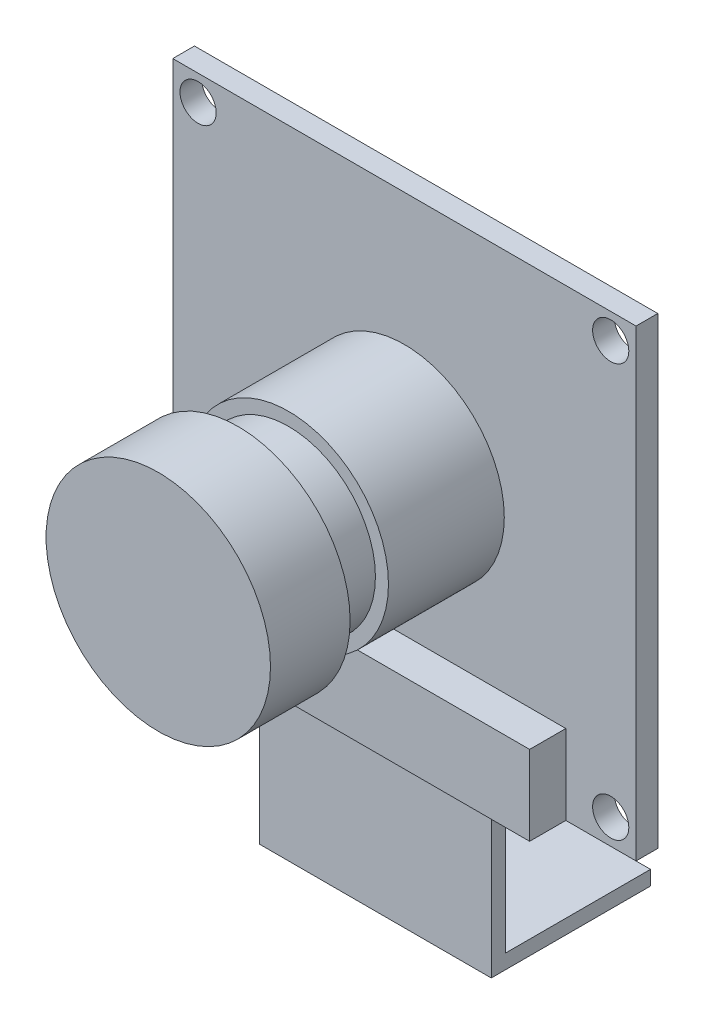
SolidWorks part; units mm, degrees
ref_plane "Спереди" through (0, 0, 0) normal (0, 0, 1) x (1, 0, 0)
ref_plane "Сверху" through (0, 0, 0) normal (0, 1, 0) x (1, 0, 0)
ref_plane "Справа" through (0, 0, 0) normal (1, 0, 0) x (0, 0, -1)
sketch "Эскиз1" plane through (0, 0, 0) normal (0, 0, 1) x (1, 0, 0)
  line L0 (0, 16) -> (0, -16) construction
  line L1 (-16, 16) -> (16, 16)
  line L2 (-16, 16) -> (-16, -16)
  line L3 (-16, -16) -> (16, -16)
  line L4 (16, 16) -> (16, -16)
  line L5 (-16, 16) -> (16, -16) construction
  line L6 (-16, -16) -> (16, 16) construction
  line L7 (-14.25, 14.25) -> (14.25, 14.25) construction
  line L8 (-14.25, 14.25) -> (-14.25, -14.25) construction
  line L9 (-14.25, -14.25) -> (14.25, -14.25) construction
  line L10 (14.25, 14.25) -> (14.25, -14.25) construction
  line L11 (-14.25, 14.25) -> (14.25, -14.25) construction
  line L12 (-14.25, -14.25) -> (14.25, 14.25) construction
  line L13 (-11.15, -10.5) -> (11.15, -10.5)
  line L14 (-11.15, -10.5) -> (-11.15, -16)
  line L15 (-11.15, -16) -> (11.15, -16)
  line L16 (11.15, -10.5) -> (11.15, -16)
  line L17 (-16, 0) -> (16, 0) construction
  circle A0 centre (0, 0) radius 6
  circle A1 centre (0, 0) radius 6.9
  circle A2 centre (0, 0) radius 7.75
  circle A4 centre (14.25, 14.25) radius 1.25
  circle A5 centre (14.25, -14.25) radius 1.25
  circle A6 centre (-14.25, -14.25) radius 1.25
  circle A7 centre (-14.25, 14.25) radius 1.25
  circle A9 centre (9.5, 0) radius 1.5
  circle A10 centre (-9.5, 0) radius 1.5
  point P0 (0, 0)
  point P6 (0, 0)
  point P23 (0, -16)
  point P34 (0, 0)
  dimension "D3" = 22.3
  dimension "D5" = 2.5
  dimension "D7" = 13.8
  dimension "D8" = 12
  dimension "D9" = 15.5
  dimension "D10" = 3
  dimension "D1" = 32
  dimension "D2" = 5.5
  dimension "D4" = 28.5
  dimension "D11" = 6.5
  dimension "D6" = 4
extrude "Плата камеры" add sketch "Эскиз1" along normal blind 1.5 contours L13 L16 L3 L4 L1 L2 L14 A7 A6 A5 A4 A2 | L16 L13 L14 L3 | A2 A1 | A1 A0 | A0 | A10 | A9 region at (0, 15.5475, 0) region at (0, -13.25, 0) region at (0, 0, 0) region at (-6.7048, 0, 0) region at (-7.5308, 0, 0) region at (-9.5, 0, 0)
extrude "Гнездо шлейфа" add sketch "Эскиз1<3>" along normal blind 2.5 from surface contours L16 L13 L14 L3 region at (0, -13.25, 0) starting at face at (0, 0, 1.5)
sketch "Эскиз1<3>" plane through (0, 0, 0) normal (0, 0, 1) x (1, 0, 0) same geometry as "Эскиз1"
extrude "Основа объектива" add sketch "Эскиз1<4>" along normal blind 8 from surface contours A1 A0 | A0 region at (0, 0, 0) region at (-6.7048, 0, 0) starting at face at (15.5, 14.25, 1.5)
sketch "Эскиз1<4>" plane through (0, 0, 0) normal (0, 0, 1) x (1, 0, 0) same geometry as "Эскиз1"
extrude "Резьбовая часть" add sketch "Эскиз1<5>" along normal blind 3.5 from surface contours A0 region at (0, 0, 0) starting at face at (6.9, 0, 9.5)
sketch "Эскиз1<5>" plane through (0, 0, 0) normal (0, 0, 1) x (1, 0, 0) same geometry as "Эскиз1"
extrude "Объектив(со стеклом)" add sketch "Эскиз1<6>" along normal blind 5.5 from surface contours A2 A1 | A1 A0 | A0 region at (0, 0, 0) region at (-6.7048, 0, 0) region at (-7.5308, 0, 0) starting at face at (6, 0, 13)
sketch "Эскиз1<6>" plane through (0, 0, 0) normal (0, 0, 1) x (1, 0, 0) same geometry as "Эскиз1"
extrude "Болты крепления объектива" add sketch "Эскиз1<7>" against normal blind 0.5 contours A9 | A10 region at (9.5, 0, 0) region at (-9.5, 0, 0)
sketch "Эскиз1<7>" plane through (0, 0, 0) normal (0, 0, 1) x (1, 0, 0) same geometry as "Эскиз1"
sketch "Эскиз2" plane through (0, -16, 0) normal (0, -1, 0) x (1, 0, 0)
  line L0 (-16, 0) -> (16, 0) construction
  line L1 (-8, 3.5) -> (8, 3.5)
  line L2 (-8, 3.5) -> (-8, 2.5)
  line L3 (-8, 2.5) -> (8, 2.5)
  line L4 (8, 3.5) -> (8, 2.5)
  line L5 (-8, 3.5) -> (8, 2.5) construction
  line L6 (-8, 2.5) -> (8, 3.5) construction
  point P0 (0, 3)
  dimension "D1" = 16
  dimension "D2" = 1
  dimension "D3" = 2.5
extrude "Шлейф" add sketch "Эскиз2" along normal blind 10 contours L4 L1 L2 L3 region at (0, -16, 3)
sketch "Эскиз3" plane through (0, 0, 2.5) normal (0, 0, -1) x (-1, 0, 0)
  line L0 (-8, -26) -> (-8, -16) construction
  line L1 (-8, -25) -> (8, -25)
  line L2 (-8, -25) -> (-8, -26)
  line L3 (-8, -26) -> (8, -26)
  line L4 (8, -25) -> (8, -26)
  line M3 (-8, -16) -> (-8, -26)
  line M4 (-8, -26) -> (8, -26)
  line M5 (8, -26) -> (8, -16)
  dimension "D1" = 1
extrude "Загиб шлейфа" add sketch "Эскиз3" along normal blind 10 contours L1 M3 M4 M5 region at (0, -25.5, 2.5)
